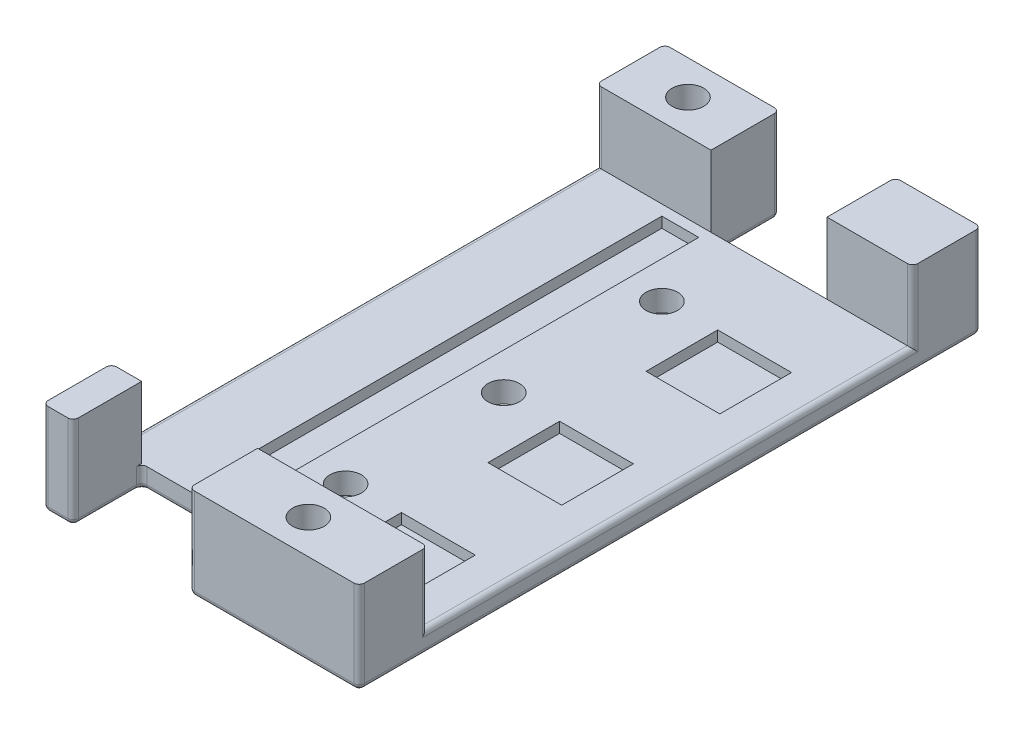
SolidWorks part; units mm, degrees
ref_plane "Front Plane" through (0, 0, 0) normal (0, 0, 1) x (1, 0, 0)
ref_plane "Top Plane" through (0, 0, 0) normal (0, 1, 0) x (1, 0, 0)
ref_plane "Right Plane" through (0, 0, 0) normal (1, 0, 0) x (0, 0, -1)
sketch "Sketch2" plane through (0, -6.7505, 0) normal (0, -1, 0) x (-1, 0, 0)
  line L0 (-30, 23) -> (0, 23) construction
  line L1 (-30, -23) -> (0, -23)
  line L2 (-30, -23) -> (-30, 23)
  line L3 (-30, 23) -> (0, 23)
  line L4 (0, -23) -> (0, 23)
  line L5 (0, -23) -> (-30, -23) construction
  line L6 (-30, -23) -> (-30, 23) construction
extrude "Boss-Extrude1" add sketch "Sketch2" along normal blind 2
sketch "Sketch4" plane through (0, -8.7505, 0) normal (0, -1, 0) x (-1, 0, 0)
  line L0 (-14.8794, 26.6064) -> (-10.8794, 26.6064) construction
  line L1 (0, 23) -> (-10.8794, 23)
  line L2 (0, 23) -> (0, 29.5)
  line L3 (0, 29.5) -> (-10.8794, 29.5)
  line L4 (-10.8794, 23) -> (-10.8794, 29.5)
  line L5 (-30, 23) -> (-21.8794, 23)
  line L6 (-30, 23) -> (-30, 29.5)
  line L7 (-30, 29.5) -> (-21.8794, 29.5)
  line L8 (-21.8794, 23) -> (-21.8794, 29.5)
  line L9 (0, -23) -> (-2.8674, -23)
  line L10 (0, -23) -> (0, -29.5)
  line L11 (0, -29.5) -> (-2.8674, -29.5)
  line L12 (-2.8674, -23) -> (-2.8674, -29.5)
  line L13 (-30, -23) -> (-13.8674, -23)
  line L14 (-30, -23) -> (-30, -29.5)
  line L15 (-30, -29.5) -> (-13.8674, -29.5)
  line L16 (-13.8674, -23) -> (-13.8674, -29.5)
  line L17 (-17.8794, 26.6064) -> (-21.8794, 26.6064) construction
  line L18 (-6.8674, -27.0854) -> (-2.8674, -27.0854) construction
  line L20 (-9.8674, -27.0854) -> (-13.8674, -27.0854) construction
  circle A0 centre (-16.3794, 26.6064) radius 1.5 construction
  circle A1 centre (-8.3674, -27.0854) radius 1.5 construction
  dimension "D1" = 4
  dimension "D2" = 6.5
  dimension "D3" = 6.5
extrude "Boss-Extrude2" add sketch "Sketch4" against normal up to surface (8.7505 mm away)
sketch "Sketch3" plane through (0, -6.7505, 0) normal (0, -1, 0) x (-1, 0, 0)
  line L0 (-38.2157, 22) -> (-7.2157, 22) construction
  line L1 (-7.2157, -22) -> (-10.7157, -22)
  line L2 (-7.2157, -22) -> (-7.2157, 22)
  line L3 (-7.2157, 22) -> (-10.7157, 22)
  line L4 (-10.7157, -22) -> (-10.7157, 22)
  line L6 (-19.2157, -6.5) -> (-26.2157, -6.5)
  line L7 (-19.2157, -6.5) -> (-19.2157, 0.3)
  line L8 (-19.2157, 0.3) -> (-26.2157, 0.3)
  line L9 (-26.2157, -6.5) -> (-26.2157, 0.3)
  line L10 (-19.2157, -21.5) -> (-26.2157, -21.5)
  line L11 (-19.2157, -21.5) -> (-19.2157, -14.7)
  line L12 (-19.2157, -14.7) -> (-26.2157, -14.7)
  line L13 (-26.2157, -21.5) -> (-26.2157, -14.7)
  line L14 (-19.2157, 8.5) -> (-26.2157, 8.5)
  line L15 (-19.2157, 8.5) -> (-19.2157, 15.3)
  line L16 (-19.2157, 15.3) -> (-26.2157, 15.3)
  line L17 (-26.2157, 8.5) -> (-26.2157, 15.3)
  dimension "D1" = 3.5
extrude "Cut-Extrude3" cut sketch "Sketch3" along normal blind 1
fillet "Fillet1" radius 0.5 28 edges at (25.9397, -8.7505, -29.5) (21.8794, -8.7505, -26.25) (16.3794, -8.7505, -23) (10.8794, -8.7505, -26.25) (5.4397, -8.7505, -29.5) (0, -8.7505, 0) (1.4337, -8.7505, 29.5) (2.8674, -8.7505, 26.25) (8.3674, -8.7505, 23) (13.8674, -8.7505, 26.25) (21.9337, -8.7505, 29.5) (30, -8.7505, 0) (21.8794, -4.3752, -29.5) (10.8794, -4.3752, -29.5) (30, -4.3752, -29.5) (30, -3.3752, -23) (30, -6.7505, 0) (30, -3.3752, 23) (30, -4.3752, 29.5) (13.8674, -4.3752, 29.5) (13.8674, -7.7505, 23) (2.8674, -7.7505, 23) (0, -3.3752, 23) (2.8674, -4.3752, 29.5) (0, -4.3752, 29.5) (0, -4.3752, -29.5) (0, -3.3752, -23) (0, -6.7505, 0)
sketch "Sketch5" plane through (0, -8.7505, 0) normal (0, -1, 0) x (-1, 0, 0)
  line L0 (-21.9337, -23) -> (-21.9337, -29.5) construction
  line L1 (-30, -23) -> (-13.8674, -23) construction
  line L2 (-30, -29.5) -> (-13.8674, -29.5) construction
  line L3 (-5.4397, 23) -> (-5.4397, 29.5) construction
  line L4 (0, 23) -> (-10.8794, 23) construction
  line L5 (0, 29.5) -> (-10.8794, 29.5) construction
  circle A0 centre (-5.4397, 26.25) radius 1.5
  circle A1 centre (-21.9337, -26.25) radius 1.5
  dimension "D1" = 3
  dimension "D2" = 3
extrude "Cut-Extrude4" cut sketch "Sketch5" against normal up to surface (8.7505 mm away)
sketch "Sketch6" plane through (0, -8.7505, 0) normal (0, -1, 0) x (1, 0, 0)
  circle A0 centre (14.2157, -15) radius 1.5 construction
  circle A1 centre (14.2157, 0) radius 1.5 construction
  circle A2 centre (14.2157, 15) radius 1.5 construction
  circle A3 centre (14.2157, -15) radius 1.5
  circle A4 centre (14.2157, 0) radius 1.5
  circle A5 centre (14.2157, 15) radius 1.5
extrude "Cut-Extrude5" cut sketch "Sketch6" against normal up to surface (2 mm away) up to face at (11.9136, -6.7505, 7.7327)
